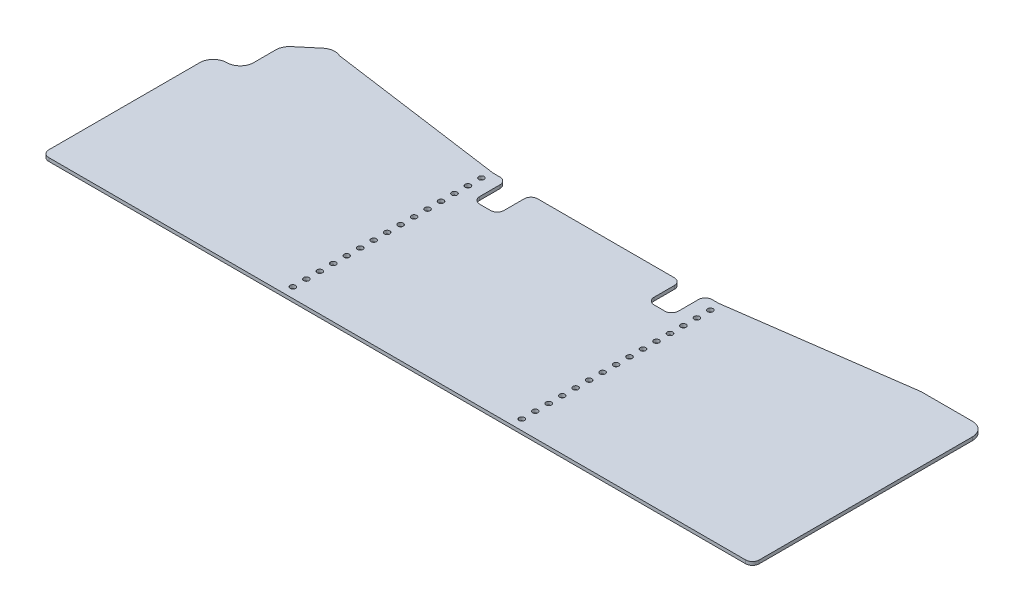
SolidWorks part; units mm, degrees
material "PC High Viscosity"
ref_plane "Front Plane" through (0, 0, 0) normal (0, 0, 1) x (1, 0, 0)
ref_plane "Top Plane" through (0, 0, 0) normal (0, 1, 0) x (1, 0, 0)
ref_plane "Right Plane" through (0, 0, 0) normal (1, 0, 0) x (0, 0, -1)
sketch "Sketch1" plane through (0, 0, 0) normal (0, 1, 0) x (1, 0, 0)
  line L0 (4.7625, 196.85) -> (4.7625, 0) construction
  line L1 (0, 0) -> (225.425, 0)
  line L2 (0, 0) -> (0, 196.85)
  line L3 (0, 196.85) -> (225.425, 196.85)
  line L4 (225.425, 0) -> (225.425, 196.85)
  line L5 (112.7125, 196.85) -> (112.7125, 0) construction
  line L6 (220.6625, 196.85) -> (220.6625, 0) construction
  line L7 (220.6625, 123.825) -> (220.6625, 111.125) construction
  circle A0 centre (4.7625, 187.325) radius 2.5527
  circle A1 centre (4.7625, 174.625) radius 2.5527
  circle A2 centre (4.7625, 161.925) radius 2.5527
  circle A3 centre (4.7625, 149.225) radius 2.5527
  circle A4 centre (4.7625, 136.525) radius 2.5527
  circle A5 centre (4.7625, 123.825) radius 2.5527
  circle A22 centre (220.6625, 123.825) radius 2.5527
  circle A23 centre (220.6625, 136.525) radius 2.5527
  circle A24 centre (220.6625, 149.225) radius 2.5527
  circle A25 centre (220.6625, 161.925) radius 2.5527
  circle A26 centre (220.6625, 174.625) radius 2.5527
  circle A27 centre (220.6625, 187.325) radius 2.5527
  circle A28 centre (4.7625, 111.125) radius 2.5527
  circle A29 centre (4.7625, 98.425) radius 2.5527
  circle A30 centre (4.7625, 85.725) radius 2.5527
  circle A31 centre (4.7625, 73.025) radius 2.5527
  circle A32 centre (4.7625, 60.325) radius 2.5527
  circle A33 centre (4.7625, 47.625) radius 2.5527
  circle A34 centre (4.7625, 34.925) radius 2.5527
  circle A35 centre (4.7625, 22.225) radius 2.5527
  circle A36 centre (4.7625, 9.525) radius 2.5527
  circle A37 centre (220.6625, 111.125) radius 2.5527
  circle A38 centre (220.6625, 98.425) radius 2.5527
  circle A39 centre (220.6625, 85.725) radius 2.5527
  circle A40 centre (220.6625, 73.025) radius 2.5527
  circle A41 centre (220.6625, 60.325) radius 2.5527
  circle A42 centre (220.6625, 47.625) radius 2.5527
  circle A43 centre (220.6625, 34.925) radius 2.5527
  circle A44 centre (220.6625, 22.225) radius 2.5527
  circle A45 centre (220.6625, 9.525) radius 2.5527
  dimension "D4" = 5.1054
  dimension "D1" = 225.425
  dimension "D2" = 196.85
  dimension "D3" = 4.7625
  dimension "D5" = 9.525
  dimension "D7" = 12.7
  dimension "D9" = 12.7
  dimension "D6" = 15
  dimension "D8" = 10
extrude "Boss-Extrude1" add sketch "Sketch1" along normal blind 3.175
fillet "Fillet1" radius 6.35 4 edges at (0, 1.5875, -196.85) (225.425, 1.5875, -196.85) (0, 1.5875, 0) (225.425, 1.5875, 0)
sketch "Sketch2" plane through (0, 3.175, 0) normal (0, 1, 0) x (1, 0, 0)
  line L0 (219.075, 196.85) -> (6.35, 196.85) construction
  line L1 (19.05, 196.85) -> (41.91, 196.85)
  line L2 (19.05, 196.85) -> (19.05, 165.1)
  line L3 (19.05, 165.1) -> (41.91, 165.1)
  line L4 (41.91, 196.85) -> (41.91, 165.1)
  line L5 (112.7125, 196.85) -> (112.7125, 0) construction
  line L6 (6.35, 0) -> (219.075, 0) construction
  line L7 (0, 190.5) -> (0, 6.35) construction
  line L8 (183.515, 196.85) -> (183.515, 165.1)
  line L9 (206.375, 165.1) -> (183.515, 165.1)
  line L10 (206.375, 196.85) -> (206.375, 165.1)
  line L11 (206.375, 196.85) -> (183.515, 196.85)
  dimension "D1" = 19.05
  dimension "D2" = 22.86
  dimension "D3" = 31.75
extrude "Cut-Extrude1" cut sketch "Sketch2" against normal through all
fillet "Fillet2" radius 6.35 8 edges at (206.375, 1.5875, -196.85) (206.375, 1.5875, -165.1) (183.515, 1.5875, -165.1) (183.515, 1.5875, -196.85) (41.91, 1.5875, -196.85) (41.91, 1.5875, -165.1) (19.05, 1.5875, -165.1) (19.05, 1.5875, -196.85)
sketch "Sketch3" plane through (0, 3.175, 0) normal (0, 1, 0) x (1, 0, 0)
  line L0 (-222.25, 263.0645) -> (-222.25, 0)
  line L2 (-222.25, 0) -> (6.35, 0)
  line L3 (-222.25, 263.0645) -> (-166.6875, 263.0645)
  line L5 (-166.6875, 263.0645) -> (-166.6875, 220.9349)
  line L6 (-168.3548, 219.2676) -> (-157.3551, 230.2673) construction
  line L7 (-166.6875, 220.9349) -> (6.35, 196.85)
  line L8 (6.35, 0) -> (219.075, 0) construction
  line L10 (-27.7821, 269.4145) -> (-233.3625, 269.4145) construction
  line L11 (112.7125, 196.85) -> (112.7125, 0) construction
  line L12 (177.165, 196.85) -> (48.26, 196.85) construction
  line L13 (225.425, 190.5) -> (225.425, 6.35)
  line L14 (212.725, 196.85) -> (219.075, 196.85)
  line L15 (189.865, 165.1) -> (200.025, 165.1)
  line L16 (183.515, 190.5) -> (183.515, 171.45)
  line L17 (392.1125, 220.9349) -> (219.075, 196.85)
  line L18 (392.1125, 263.0645) -> (392.1125, 220.9349)
  line L19 (447.675, 263.0645) -> (392.1125, 263.0645)
  line L20 (447.675, 0) -> (219.075, 0)
  line L21 (219.075, 196.85) -> (212.725, 196.85)
  line L22 (206.375, 190.5) -> (206.375, 171.45)
  line L23 (200.025, 165.1) -> (189.865, 165.1)
  line L24 (183.515, 171.45) -> (183.515, 190.5)
  line L25 (177.165, 196.85) -> (48.26, 196.85)
  line L26 (41.91, 190.5) -> (41.91, 171.45)
  line L27 (35.56, 165.1) -> (25.4, 165.1)
  line L28 (19.05, 171.45) -> (19.05, 190.5)
  line L29 (12.7, 196.85) -> (6.35, 196.85)
  line L30 (0, 190.5) -> (0, 6.35)
  line L31 (6.35, 0) -> (219.075, 0)
  line L32 (225.425, 6.35) -> (225.425, 190.5)
  line L33 (219.075, 196.85) -> (212.725, 196.85)
  line L34 (206.375, 190.5) -> (206.375, 171.45)
  line L35 (200.025, 165.1) -> (189.865, 165.1)
  line L36 (183.515, 171.45) -> (183.515, 190.5)
  line L38 (41.91, 190.5) -> (41.91, 171.45)
  line L39 (35.56, 165.1) -> (25.4, 165.1)
  line L41 (12.7, 196.85) -> (6.35, 196.85)
  line L42 (0, 190.5) -> (0, 6.35)
  line L44 (225.425, 6.35) -> (225.425, 190.5)
  line L45 (447.675, 263.0645) -> (447.675, 0)
  circle A0 centre (-173.0375, 256.7145) radius 2.4892 construction
  arc A1 (225.425, 6.35) -> (219.075, 0) centre (219.075, 6.35) cw
  arc A2 (219.075, 196.85) -> (225.425, 190.5) centre (219.075, 190.5) cw
  arc A3 (206.375, 190.5) -> (212.725, 196.85) centre (212.725, 190.5) cw
  arc A4 (206.375, 171.45) -> (200.025, 165.1) centre (200.025, 171.45) cw
  arc A5 (189.865, 165.1) -> (183.515, 171.45) centre (189.865, 171.45) cw
  arc A6 (177.165, 196.85) -> (183.515, 190.5) centre (177.165, 190.5) cw
  arc A12 (212.725, 196.85) -> (206.375, 190.5) centre (212.725, 190.5) ccw
  arc A13 (200.025, 165.1) -> (206.375, 171.45) centre (200.025, 171.45) ccw
  arc A14 (183.515, 171.45) -> (189.865, 165.1) centre (189.865, 171.45) ccw
  arc A15 (183.515, 190.5) -> (177.165, 196.85) centre (177.165, 190.5) ccw
  arc A16 (48.26, 196.85) -> (41.91, 190.5) centre (48.26, 190.5) ccw
  arc A17 (35.56, 165.1) -> (41.91, 171.45) centre (35.56, 171.45) ccw
  arc A18 (19.05, 171.45) -> (25.4, 165.1) centre (25.4, 171.45) ccw
  arc A19 (19.05, 190.5) -> (12.7, 196.85) centre (12.7, 190.5) ccw
  arc A20 (6.35, 196.85) -> (0, 190.5) centre (6.35, 190.5) ccw
  arc A21 (0, 6.35) -> (6.35, 0) centre (6.35, 6.35) ccw
  arc A22 (219.075, 0) -> (225.425, 6.35) centre (219.075, 6.35) ccw
  arc A23 (225.425, 190.5) -> (219.075, 196.85) centre (219.075, 190.5) ccw
  arc A24 (212.725, 196.85) -> (206.375, 190.5) centre (212.725, 190.5) ccw
  arc A25 (200.025, 165.1) -> (206.375, 171.45) centre (200.025, 171.45) ccw
  arc A26 (183.515, 171.45) -> (189.865, 165.1) centre (189.865, 171.45) ccw
  arc A27 (183.515, 190.5) -> (177.165, 196.85) centre (177.165, 190.5) ccw
  arc A28 (48.26, 196.85) -> (41.91, 190.5) centre (48.26, 190.5) ccw
  arc A29 (35.56, 165.1) -> (41.91, 171.45) centre (35.56, 171.45) ccw
  arc A30 (19.05, 171.45) -> (25.4, 165.1) centre (25.4, 171.45) ccw
  arc A31 (19.05, 190.5) -> (12.7, 196.85) centre (12.7, 190.5) ccw
  arc A32 (6.35, 196.85) -> (0, 190.5) centre (6.35, 190.5) ccw
  arc A33 (0, 6.35) -> (6.35, 0) centre (6.35, 6.35) ccw
  arc A34 (219.075, 0) -> (225.425, 6.35) centre (219.075, 6.35) ccw
  arc A35 (225.425, 190.5) -> (219.075, 196.85) centre (219.075, 190.5) ccw
  dimension "D1" = 0
  dimension "D2" = 222.25
  dimension "D3" = 6.35
  dimension "D4" = 6.35
extrude "Boss-Extrude2" add sketch "Sketch3" against normal up to surface (3.175 mm away) contours A33 L42 A32 L7 L5 L3 L0 L2 | L17 A2 L13 A1 L20 L45 L19 L18 region at (-117.1873, 3.175, -112.6737) region at (342.6123, 3.175, -112.6737) up to face at (112.7125, 0, -153.4583)
fillet "Fillet3" radius 6.35 10 edges at (-166.6875, 1.5875, -220.9349) (-166.6875, 1.5875, -263.0645) (-222.25, 1.5875, -263.0645) (-222.25, 1.5875, 0) (447.675, 1.5875, -263.0645) (392.1125, 1.5875, -263.0645) (392.1125, 1.5875, -220.9349) (219.075, 1.5875, -196.85) (6.35, 1.5875, -196.85) (447.675, 1.5875, 0)
sketch "Sketch4" plane through (0, 3.175, 0) normal (0, 1, 0) x (1, 0, 0)
  line L0 (112.7125, 0) -> (112.7125, 196.85) construction
  line L1 (-215.9, 0) -> (441.325, 0) construction
  line L2 (177.165, 196.85) -> (48.26, 196.85) construction
  circle A1 centre (-46.0375, 256.7145) radius 2.4892
  circle A2 centre (-46.0375, 256.7145) radius 2.4892
  circle A3 centre (-58.7375, 256.7145) radius 2.4892
  circle A4 centre (-58.7375, 256.7145) radius 2.4892
  circle A5 centre (-71.4375, 256.7145) radius 2.4892
  circle A6 centre (-71.4375, 256.7145) radius 2.4892
  circle A7 centre (-84.1375, 256.7145) radius 2.4892
  circle A8 centre (-84.1375, 256.7145) radius 2.4892
  circle A9 centre (-96.8375, 256.7145) radius 2.4892
  circle A10 centre (-96.8375, 256.7145) radius 2.4892
  circle A11 centre (-109.5375, 256.7145) radius 2.4892
  circle A12 centre (-109.5375, 256.7145) radius 2.4892
  circle A13 centre (-122.2375, 256.7145) radius 2.4892
  circle A14 centre (-122.2375, 256.7145) radius 2.4892
  circle A15 centre (-134.9375, 256.7145) radius 2.4892
  circle A16 centre (-134.9375, 256.7145) radius 2.4892
  circle A17 centre (-147.6375, 256.7145) radius 2.4892
  circle A18 centre (-147.6375, 256.7145) radius 2.4892
  circle A19 centre (-160.3375, 256.7145) radius 2.4892
  circle A20 centre (-160.3375, 256.7145) radius 2.4892
  circle A21 centre (-173.0375, 256.7145) radius 2.4892
  circle A22 centre (-173.0375, 256.7145) radius 2.4892
  circle A23 centre (-185.7375, 256.7145) radius 2.4892
  circle A24 centre (-185.7375, 256.7145) radius 2.4892
  circle A25 centre (-198.4375, 256.7145) radius 2.4892
  circle A26 centre (-198.4375, 256.7145) radius 2.4892
  circle A27 centre (-211.1375, 256.7145) radius 2.4892
  circle A28 centre (-211.1375, 256.7145) radius 2.4892
  circle A29 centre (-223.8375, 256.7145) radius 2.4892
  circle A30 centre (-223.8375, 256.7145) radius 2.4892
  circle A31 centre (-20.6375, 256.7145) radius 2.4892
  circle A32 centre (-20.6375, 256.7145) radius 2.4892
  circle A33 centre (-33.3375, 256.7145) radius 2.4892
  circle A34 centre (-33.3375, 256.7145) radius 2.4892
  circle A255 centre (449.2625, 256.7145) radius 2.4892
  circle A256 centre (436.5625, 256.7145) radius 2.4892
  circle A257 centre (423.8625, 256.7145) radius 2.4892
  circle A258 centre (411.1625, 256.7145) radius 2.4892
  dimension "D1" = 0
  dimension "D2" = 0
  dimension "D3" = 0
  dimension "D4" = 0
  dimension "D5" = 0
  dimension "D6" = 0
  dimension "D7" = 0
  dimension "D8" = 0
  dimension "D9" = 0
  dimension "D10" = 0
  dimension "D11" = 0
  dimension "D12" = 0
  dimension "D13" = 0
  dimension "D14" = 0
  dimension "D15" = 0
  dimension "D16" = 0
  dimension "D17" = 0
extrude "Cut-Extrude2" cut sketch "Sketch4" against normal through all contours A28 | A30 | A26 | A24 | A258 | A257 | A256 | A255 region at (-185.7375, 3.175, -256.7145) region at (-198.4375, 3.175, -256.7145) region at (-211.1375, 3.175, -256.7145) region at (-223.8375, 3.175, -256.7145) region at (449.2625, 3.175, -256.7145) region at (436.5625, 3.175, -256.7145) region at (423.8625, 3.175, -256.7145) region at (411.1625, 3.175, -256.7145)
sketch "Sketch5" plane through (0, 3.175, 0) normal (0, 1, 0) x (1, 0, 0)
  line L0 (-166.6875, 226.4622) -> (-196.85, 201.0622)
  line L1 (-196.85, 201.0622) -> (-196.85, 161.4645)
  line L3 (-196.85, 161.4645) -> (-222.25, 161.4645)
  line L21 (441.325, 263.0645) -> (398.4625, 263.0645)
  line L22 (392.1125, 256.7145) -> (392.1125, 226.4622)
  line L23 (386.6379, 220.1729) -> (219.5106, 196.9106)
  line L24 (218.6352, 196.85) -> (212.725, 196.85)
  line L25 (206.375, 190.5) -> (206.375, 171.45)
  line L26 (200.025, 165.1) -> (189.865, 165.1)
  line L27 (183.515, 171.45) -> (183.515, 190.5)
  line L28 (177.165, 196.85) -> (48.26, 196.85)
  line L29 (41.91, 190.5) -> (41.91, 171.45)
  line L30 (35.56, 165.1) -> (25.4, 165.1)
  line L31 (19.05, 171.45) -> (19.05, 190.5)
  line L32 (12.7, 196.85) -> (6.7898, 196.85)
  line L33 (5.9144, 196.9106) -> (-161.2129, 220.1729)
  line L34 (-166.6875, 226.4622) -> (-166.6875, 256.7145)
  line L35 (-173.0375, 263.0645) -> (-215.9, 263.0645)
  line L36 (-222.25, 254.7972) -> (-222.25, 6.35)
  line L37 (-215.9, 0) -> (441.325, 0)
  line L38 (447.675, 6.35) -> (447.675, 254.7972)
  line L39 (441.325, 263.0645) -> (398.4625, 263.0645)
  line L40 (392.1125, 256.7145) -> (392.1125, 226.4622)
  line L41 (386.6379, 220.1729) -> (219.5106, 196.9106)
  line L42 (218.6352, 196.85) -> (212.725, 196.85)
  line L43 (206.375, 190.5) -> (206.375, 171.45)
  line L44 (200.025, 165.1) -> (189.865, 165.1)
  line L45 (183.515, 171.45) -> (183.515, 190.5)
  line L46 (177.165, 196.85) -> (48.26, 196.85)
  line L47 (41.91, 190.5) -> (41.91, 171.45)
  line L48 (35.56, 165.1) -> (25.4, 165.1)
  line L49 (19.05, 171.45) -> (19.05, 190.5)
  line L50 (12.7, 196.85) -> (6.7898, 196.85)
  line L51 (5.9144, 196.9106) -> (-161.2129, 220.1729)
  line L52 (-166.6875, 226.4622) -> (-166.6875, 256.7145)
  line L53 (-173.0375, 263.0645) -> (-215.9, 263.0645)
  line L54 (-222.25, 254.7972) -> (-222.25, 6.35)
  line L55 (-215.9, 0) -> (441.325, 0)
  line L56 (447.675, 6.35) -> (447.675, 254.7972)
  arc A20 (447.4434, 258.4137) -> (447.675, 254.7972) centre (449.2625, 256.7145) ccw
  arc A21 (447.4434, 258.4137) -> (441.325, 263.0645) centre (441.325, 256.7145) ccw
  arc A22 (398.4625, 263.0645) -> (392.1125, 256.7145) centre (398.4625, 256.7145) ccw
  arc A23 (386.6379, 220.1729) -> (392.1125, 226.4622) centre (385.7625, 226.4622) ccw
  arc A24 (218.6352, 196.85) -> (219.5106, 196.9106) centre (218.6352, 203.2) ccw
  arc A25 (212.725, 196.85) -> (206.375, 190.5) centre (212.725, 190.5) ccw
  arc A26 (200.025, 165.1) -> (206.375, 171.45) centre (200.025, 171.45) ccw
  arc A27 (183.515, 171.45) -> (189.865, 165.1) centre (189.865, 171.45) ccw
  arc A28 (183.515, 190.5) -> (177.165, 196.85) centre (177.165, 190.5) ccw
  arc A29 (48.26, 196.85) -> (41.91, 190.5) centre (48.26, 190.5) ccw
  arc A30 (35.56, 165.1) -> (41.91, 171.45) centre (35.56, 171.45) ccw
  arc A31 (19.05, 171.45) -> (25.4, 165.1) centre (25.4, 171.45) ccw
  arc A32 (19.05, 190.5) -> (12.7, 196.85) centre (12.7, 190.5) ccw
  arc A33 (5.9144, 196.9106) -> (6.7898, 196.85) centre (6.7898, 203.2) ccw
  arc A34 (-166.6875, 226.4622) -> (-161.2129, 220.1729) centre (-160.3375, 226.4622) ccw
  arc A35 (-166.6875, 256.7145) -> (-173.0375, 263.0645) centre (-173.0375, 256.7145) ccw
  arc A36 (-215.9, 263.0645) -> (-222.0184, 258.4137) centre (-215.9, 256.7145) ccw
  arc A37 (-222.25, 254.7972) -> (-222.0184, 258.4137) centre (-223.8375, 256.7145) ccw
  arc A38 (-222.25, 6.35) -> (-215.9, 0) centre (-215.9, 6.35) ccw
  arc A39 (441.325, 0) -> (447.675, 6.35) centre (441.325, 6.35) ccw
  arc A40 (447.4434, 258.4137) -> (447.675, 254.7972) centre (449.2625, 256.7145) ccw
  arc A41 (447.4434, 258.4137) -> (441.325, 263.0645) centre (441.325, 256.7145) ccw
  arc A42 (398.4625, 263.0645) -> (392.1125, 256.7145) centre (398.4625, 256.7145) ccw
  arc A43 (386.6379, 220.1729) -> (392.1125, 226.4622) centre (385.7625, 226.4622) ccw
  arc A44 (218.6352, 196.85) -> (219.5106, 196.9106) centre (218.6352, 203.2) ccw
  arc A45 (212.725, 196.85) -> (206.375, 190.5) centre (212.725, 190.5) ccw
  arc A46 (200.025, 165.1) -> (206.375, 171.45) centre (200.025, 171.45) ccw
  arc A47 (183.515, 171.45) -> (189.865, 165.1) centre (189.865, 171.45) ccw
  arc A48 (183.515, 190.5) -> (177.165, 196.85) centre (177.165, 190.5) ccw
  arc A49 (48.26, 196.85) -> (41.91, 190.5) centre (48.26, 190.5) ccw
  arc A50 (35.56, 165.1) -> (41.91, 171.45) centre (35.56, 171.45) ccw
  arc A51 (19.05, 171.45) -> (25.4, 165.1) centre (25.4, 171.45) ccw
  arc A52 (19.05, 190.5) -> (12.7, 196.85) centre (12.7, 190.5) ccw
  arc A53 (5.9144, 196.9106) -> (6.7898, 196.85) centre (6.7898, 203.2) ccw
  arc A54 (-166.6875, 226.4622) -> (-161.2129, 220.1729) centre (-160.3375, 226.4622) ccw
  arc A55 (-166.6875, 256.7145) -> (-173.0375, 263.0645) centre (-173.0375, 256.7145) ccw
  arc A56 (-215.9, 263.0645) -> (-222.0184, 258.4137) centre (-215.9, 256.7145) ccw
  arc A57 (-222.25, 254.7972) -> (-222.0184, 258.4137) centre (-223.8375, 256.7145) ccw
  arc A58 (-222.25, 6.35) -> (-215.9, 0) centre (-215.9, 6.35) ccw
  arc A59 (441.325, 0) -> (447.675, 6.35) centre (441.325, 6.35) ccw
  dimension "D1" = 0
  dimension "D2" = 101.6
  dimension "D3" = 25.4
  dimension "D4" = 25.4
extrude "Cut-Extrude3" cut sketch "Sketch5" against normal through all contours A57 L54 L1 A54 L52 A55 L53 A56 region at (-199.878, 3.175, -221.4342)
fillet "Fillet4" radius 12.7 1 edges at (-166.6875, 1.5875, -226.4622)
fillet "Fillet5" radius 12.7 5 edges at (-196.85, 1.5875, -201.0622) (-196.85, 1.5875, -161.4645) (447.675, 1.5875, -254.7972) (447.4434, 1.5875, -258.4137) (-222.25, 1.5875, -161.4645)
sketch "Sketch6" plane through (0, 3.175, 0) normal (0, 1, 0) x (1, 0, 0)
  line L0 (386.6379, 220.1729) -> (447.675, 220.1729)
  line L1 (447.675, 251.559) -> (447.675, 6.35) construction
  line L20 (-175.9706, 218.6449) -> (-192.3305, 204.8681)
  line L21 (-196.85, 195.1537) -> (-196.85, 174.1645)
  line L22 (-222.25, 148.7645) -> (-222.25, 6.35)
  line L23 (-215.9, 0) -> (441.325, 0)
  line L24 (447.675, 6.35) -> (447.675, 251.559)
  line L25 (435.4643, 263.0645) -> (398.4625, 263.0645)
  line L26 (392.1125, 256.7145) -> (392.1125, 226.4622)
  line L27 (386.6379, 220.1729) -> (219.5106, 196.9106)
  line L28 (218.6352, 196.85) -> (212.725, 196.85)
  line L29 (206.375, 190.5) -> (206.375, 171.45)
  line L30 (200.025, 165.1) -> (189.865, 165.1)
  line L31 (183.515, 171.45) -> (183.515, 190.5)
  line L32 (177.165, 196.85) -> (48.26, 196.85)
  line L33 (41.91, 190.5) -> (41.91, 171.45)
  line L34 (35.56, 165.1) -> (25.4, 165.1)
  line L35 (19.05, 171.45) -> (19.05, 190.5)
  line L36 (12.7, 196.85) -> (6.7898, 196.85)
  line L37 (5.9144, 196.9106) -> (-161.2129, 220.1729)
  line L38 (-175.9706, 218.6449) -> (-192.3305, 204.8681)
  line L39 (-196.85, 195.1537) -> (-196.85, 174.1645)
  line L40 (-222.25, 148.7645) -> (-222.25, 6.35)
  line L41 (-215.9, 0) -> (441.325, 0)
  line L42 (447.675, 6.35) -> (447.675, 251.559)
  line L43 (435.4643, 263.0645) -> (398.4625, 263.0645)
  line L44 (392.1125, 256.7145) -> (392.1125, 226.4622)
  line L45 (386.6379, 220.1729) -> (219.5106, 196.9106)
  line L46 (218.6352, 196.85) -> (212.725, 196.85)
  line L47 (206.375, 190.5) -> (206.375, 171.45)
  line L48 (200.025, 165.1) -> (189.865, 165.1)
  line L49 (183.515, 171.45) -> (183.515, 190.5)
  line L50 (177.165, 196.85) -> (48.26, 196.85)
  line L51 (41.91, 190.5) -> (41.91, 171.45)
  line L52 (35.56, 165.1) -> (25.4, 165.1)
  line L53 (19.05, 171.45) -> (19.05, 190.5)
  line L54 (12.7, 196.85) -> (6.7898, 196.85)
  line L55 (5.9144, 196.9106) -> (-161.2129, 220.1729)
  arc A21 (-192.3305, 204.8681) -> (-196.85, 195.1537) centre (-184.15, 195.1537) ccw
  arc A22 (-209.55, 161.4645) -> (-196.85, 174.1645) centre (-209.55, 174.1645) ccw
  arc A23 (-209.55, 161.4645) -> (-222.25, 148.7645) centre (-209.55, 148.7645) ccw
  arc A24 (-222.25, 6.35) -> (-215.9, 0) centre (-215.9, 6.35) ccw
  arc A25 (441.325, 0) -> (447.675, 6.35) centre (441.325, 6.35) ccw
  arc A26 (447.675, 251.559) -> (446.9566, 255.7699) centre (434.975, 251.559) ccw
  arc A27 (446.9566, 255.7699) -> (435.4643, 263.0645) centre (435.4643, 250.3645) ccw
  arc A28 (398.4625, 263.0645) -> (392.1125, 256.7145) centre (398.4625, 256.7145) ccw
  arc A29 (386.6379, 220.1729) -> (392.1125, 226.4622) centre (385.7625, 226.4622) ccw
  arc A30 (218.6352, 196.85) -> (219.5106, 196.9106) centre (218.6352, 203.2) ccw
  arc A31 (212.725, 196.85) -> (206.375, 190.5) centre (212.725, 190.5) ccw
  arc A32 (200.025, 165.1) -> (206.375, 171.45) centre (200.025, 171.45) ccw
  arc A33 (183.515, 171.45) -> (189.865, 165.1) centre (189.865, 171.45) ccw
  arc A34 (183.515, 190.5) -> (177.165, 196.85) centre (177.165, 190.5) ccw
  arc A35 (48.26, 196.85) -> (41.91, 190.5) centre (48.26, 190.5) ccw
  arc A36 (35.56, 165.1) -> (41.91, 171.45) centre (35.56, 171.45) ccw
  arc A37 (19.05, 171.45) -> (25.4, 165.1) centre (25.4, 171.45) ccw
  arc A38 (19.05, 190.5) -> (12.7, 196.85) centre (12.7, 190.5) ccw
  arc A39 (5.9144, 196.9106) -> (6.7898, 196.85) centre (6.7898, 203.2) ccw
  arc A40 (-162.8217, 220.6183) -> (-161.2129, 220.1729) centre (-160.3375, 226.4622) ccw
  arc A41 (-162.8217, 220.6183) -> (-175.9706, 218.6449) centre (-167.7901, 208.9305) ccw
  arc A42 (-192.3305, 204.8681) -> (-196.85, 195.1537) centre (-184.15, 195.1537) ccw
  arc A43 (-209.55, 161.4645) -> (-196.85, 174.1645) centre (-209.55, 174.1645) ccw
  arc A44 (-209.55, 161.4645) -> (-222.25, 148.7645) centre (-209.55, 148.7645) ccw
  arc A45 (-222.25, 6.35) -> (-215.9, 0) centre (-215.9, 6.35) ccw
  arc A46 (441.325, 0) -> (447.675, 6.35) centre (441.325, 6.35) ccw
  arc A47 (447.675, 251.559) -> (446.9566, 255.7699) centre (434.975, 251.559) ccw
  arc A48 (446.9566, 255.7699) -> (435.4643, 263.0645) centre (435.4643, 250.3645) ccw
  arc A49 (398.4625, 263.0645) -> (392.1125, 256.7145) centre (398.4625, 256.7145) ccw
  arc A50 (386.6379, 220.1729) -> (392.1125, 226.4622) centre (385.7625, 226.4622) ccw
  arc A51 (218.6352, 196.85) -> (219.5106, 196.9106) centre (218.6352, 203.2) ccw
  arc A52 (212.725, 196.85) -> (206.375, 190.5) centre (212.725, 190.5) ccw
  arc A53 (200.025, 165.1) -> (206.375, 171.45) centre (200.025, 171.45) ccw
  arc A54 (183.515, 171.45) -> (189.865, 165.1) centre (189.865, 171.45) ccw
  arc A55 (183.515, 190.5) -> (177.165, 196.85) centre (177.165, 190.5) ccw
  arc A56 (48.26, 196.85) -> (41.91, 190.5) centre (48.26, 190.5) ccw
  arc A57 (35.56, 165.1) -> (41.91, 171.45) centre (35.56, 171.45) ccw
  arc A58 (19.05, 171.45) -> (25.4, 165.1) centre (25.4, 171.45) ccw
  arc A59 (19.05, 190.5) -> (12.7, 196.85) centre (12.7, 190.5) ccw
  arc A60 (5.9144, 196.9106) -> (6.7898, 196.85) centre (6.7898, 203.2) ccw
  arc A61 (-162.8217, 220.6183) -> (-161.2129, 220.1729) centre (-160.3375, 226.4622) ccw
  arc A62 (-162.8217, 220.6183) -> (-175.9706, 218.6449) centre (-167.7901, 208.9305) ccw
  dimension "D1" = 0
extrude "Cut-Extrude4" cut sketch "Sketch6" against normal through all contours A50 L0 L42 A47 A48 L43 A49 L44 region at (419.5699, 3.175, -241.2337)
fillet "Fillet6" radius 12.7 2 edges at (386.6379, 1.5875, -220.1729) (447.675, 1.5875, -220.1729)
